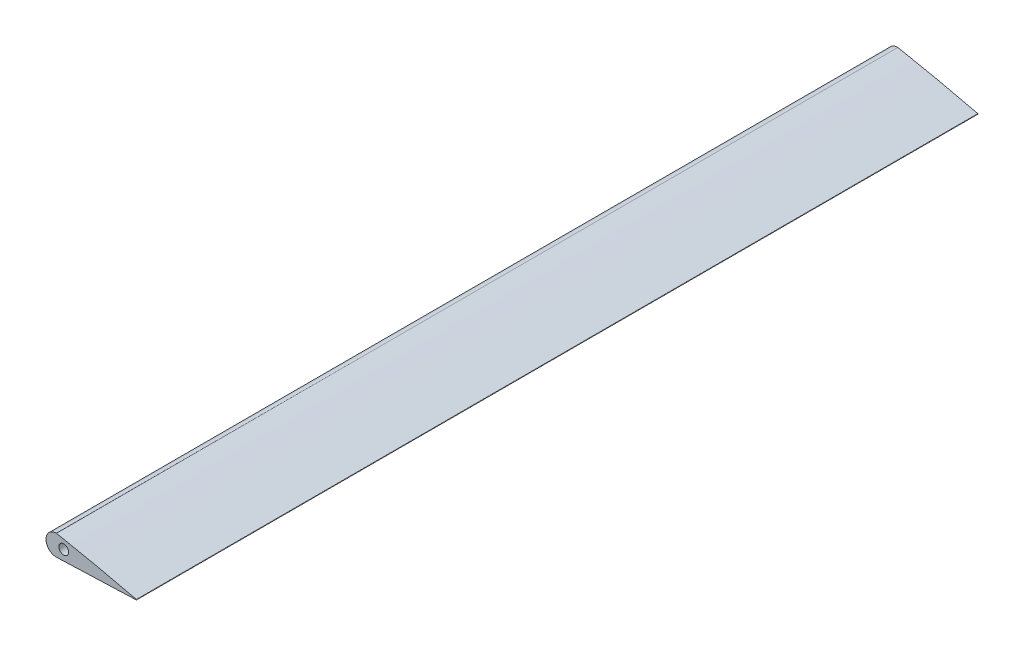
SolidWorks part; units mm, degrees
ref_plane "Front Plane" through (0, 0, 0) normal (0, 0, 1) x (1, 0, 0)
ref_plane "Top Plane" through (0, 0, 0) normal (0, 1, 0) x (1, 0, 0)
ref_plane "Right Plane" through (0, 0, 0) normal (1, 0, 0) x (0, 0, -1)
curve "Curve1"
  spline degree 3 poles (164, 0.0982, 0) (163.4533, 0.2279, 0) (162.3601, 0.4871, 0) (160.7202, 0.8748, 0) (159.0803, 1.2611, 0) (156.8943, 1.7719, 0) (154.162, 2.401, 0) (150.8818, 3.1375, 0) (147.6017, 3.8566, 0) (144.3217, 4.5599, 0) (141.0417, 5.2462, 0) (137.7618, 5.9156, 0) (134.4817, 6.5665, 0) (131.2018, 7.1999, 0) (127.9217, 7.8138, 0) (124.6417, 8.4092, 0) (121.3616, 8.9846, 0) (118.0816, 9.5413, 0) (114.8016, 10.0781, 0) (111.5216, 10.595, 0) (108.2417, 11.091, 0) (104.9617, 11.5629, 0) (101.6818, 12.0102, 0) (98.4017, 12.4297, 0) (95.1217, 12.8205, 0) (91.8415, 13.1818, 0) (88.5614, 13.5136, 0) (85.2813, 13.8159, 0) (82.0012, 14.0887, 0) (78.7211, 14.3317, 0) (75.441, 14.5432, 0) (72.1609, 14.7199, 0) (68.8807, 14.8594, 0) (65.6005, 14.9592, 0) (62.3202, 15.0161, 0) (59.04, 15.033, 0) (55.7598, 15.0128, 0) (52.4797, 14.9596, 0) (49.1996, 14.8756, 0) (45.9192, 14.7668, 0) (42.6385, 14.6188, 0) (39.3574, 14.416, 0) (36.0758, 14.1416, 0) (32.7935, 13.7797, 0) (29.5117, 13.3118, 0) (26.2304, 12.7369, 0) (22.9482, 12.0591, 0) (19.664, 11.2714, 0) (16.3781, 10.3517, 0) (13.0927, 9.2716, 0) (10.3582, 8.2399, 0) (8.1787, 7.2692, 0) (6.5271, 6.4236, 0) (4.8606, 5.419, 0) (3.3222, 4.2467, 0) (2.1668, 3.1342, 0) (1.2848, 2.24, 0) (0.7248, 1.5863, 0) (0.3565, 1.0237, 0) (0.1763, 0.6552, 0) (0.0613, 0.3376, 0) (-0.0429, -0.1211, 0) (0.0101, -0.5985, 0) (0.1762, -1.0141, 0) (0.3547, -1.3445, 0) (0.7171, -1.8262, 0) (1.2698, -2.3368, 0) (2.1318, -2.9202, 0) (3.3549, -3.3928, 0) (4.9153, -3.7072, 0) (6.5542, -4.033, 0) (8.1953, -4.2835, 0) (10.3823, -4.5154, 0) (13.1186, -4.6727, 0) (16.3989, -4.8285, 0) (19.6795, -4.9221, 0) (22.9598, -4.9665, 0) (26.2401, -4.9679, 0) (29.5202, -4.9328, 0) (32.8003, -4.8689, 0) (36.0803, -4.7827, 0) (39.3602, -4.679, 0) (42.6401, -4.563, 0) (45.9201, -4.4399, 0) (49.2, -4.3141, 0) (52.48, -4.1907, 0) (55.76, -4.07, 0) (59.04, -3.9501, 0) (62.32, -3.8313, 0) (65.6, -3.7121, 0) (68.88, -3.5923, 0) (72.16, -3.4722, 0) (75.44, -3.3513, 0) (78.72, -3.2307, 0) (82, -3.1097, 0) (85.28, -2.989, 0) (88.56, -2.8685, 0) (91.84, -2.7482, 0) (95.12, -2.6278, 0) (98.4, -2.5074, 0) (101.68, -2.387, 0) (104.96, -2.2667, 0) (108.24, -2.1461, 0) (111.52, -2.0255, 0) (114.8, -1.9053, 0) (118.08, -1.7846, 0) (121.36, -1.6644, 0) (124.64, -1.5437, 0) (127.92, -1.4234, 0) (131.2, -1.3027, 0) (134.48, -1.1825, 0) (137.76, -1.0618, 0) (141.04, -0.9416, 0) (144.32, -0.8209, 0) (147.6, -0.7007, 0) (150.88, -0.58, 0) (154.16, -0.4598, 0) (156.8933, -0.3592, 0) (159.08, -0.279, 0) (160.72, -0.2188, 0) (162.36, -0.1586, 0) (163.4533, -0.1184, 0) (164, -0.0982, 0) knots 0 0 0 0 0.005028 0.010055 0.015081 0.020105 0.030145 0.040174 0.050191 0.060198 0.070194 0.08018 0.090156 0.100121 0.110076 0.12002 0.129954 0.139879 0.149793 0.159699 0.169594 0.17948 0.189355 0.199219 0.209073 0.218917 0.228751 0.238577 0.248396 0.258207 0.268012 0.277811 0.287604 0.297393 0.307179 0.316964 0.326749 0.336535 0.346322 0.356113 0.365908 0.375711 0.385531 0.395376 0.405259 0.415192 0.425184 0.435248 0.445412 0.455711 0.466191 0.471552 0.477055 0.482787 0.488946 0.494316 0.497126 0.500187 0.502001 0.503128 0.50385 0.50502 0.507318 0.507987 0.509024 0.510668 0.513358 0.515716 0.519949 0.524973 0.529954 0.534903 0.539824 0.54963 0.559425 0.569214 0.579 0.588784 0.59857 0.608356 0.618144 0.627933 0.637724 0.647515 0.657307 0.667099 0.67689 0.686681 0.696472 0.706263 0.716054 0.725846 0.735637 0.745428 0.755219 0.765011 0.774802 0.784593 0.794384 0.804176 0.813967 0.823758 0.833549 0.84334 0.853132 0.862923 0.872714 0.882505 0.892297 0.902088 0.911879 0.92167 0.931461 0.941253 0.951044 0.960835 0.970626 0.980418 0.985313 0.990209 0.995104 1 1 1 1
sketch "Sketch2" plane through (0, 0, 0) normal (0, 0, 1) x (1, 0, 0)
  line L0 (0, 0) -> (164.0777, 0) construction
  arc A0 (164, 0.0982) -> (164, -0.0982) centre (163.9767, 0) cw
  spline S0 degree 3 poles (1530.9533, 3736.1944) (464.6242, -85.7653) (314.6036, -35.5074) (160.7202, 0.8748) (159.0803, 1.2611) (156.8943, 1.7719) (154.162, 2.401) (150.8818, 3.1375) (147.6017, 3.8566) (144.3217, 4.5599) (141.0417, 5.2462) (137.7618, 5.9156) (134.4817, 6.5665) (131.2018, 7.1999) (127.9217, 7.8138) (124.6417, 8.4092) (121.3616, 8.9846) (118.0816, 9.5413) (114.8016, 10.0781) (111.5216, 10.595) (108.2417, 11.091) (104.9617, 11.5629) (101.6818, 12.0102) (98.4017, 12.4297) (95.1217, 12.8205) (91.8415, 13.1818) (88.5614, 13.5136) (85.2813, 13.8159) (82.0012, 14.0887) (78.7211, 14.3317) (75.441, 14.5432) (72.1609, 14.7199) (68.8807, 14.8594) (65.6005, 14.9592) (62.3202, 15.0161) (59.04, 15.033) (55.7598, 15.0128) (52.4797, 14.9596) (49.1996, 14.8756) (45.9192, 14.7668) (42.6385, 14.6188) (39.3574, 14.416) (36.0758, 14.1416) (32.7935, 13.7797) (29.5117, 13.3118) (26.2304, 12.7369) (22.9482, 12.0591) (19.664, 11.2714) (16.3781, 10.3517) (13.0927, 9.2716) (10.3582, 8.2399) (8.1787, 7.2692) (6.5271, 6.4236) (4.8606, 5.419) (3.3222, 4.2467) (2.1668, 3.1342) (1.2848, 2.24) (0.7248, 1.5863) (0.3565, 1.0237) (0.1763, 0.6552) (0.0613, 0.3376) (-0.0429, -0.1211) (0.0101, -0.5985) (0.1762, -1.0141) (0.3547, -1.3445) (0.7171, -1.8262) (1.2698, -2.3368) (2.1318, -2.9202) (3.3549, -3.3928) (4.9153, -3.7072) (6.5542, -4.033) (8.1953, -4.2835) (10.3823, -4.5154) (13.1186, -4.6727) (16.3989, -4.8285) (19.6795, -4.9221) (22.9598, -4.9665) (26.2401, -4.9679) (29.5202, -4.9328) (32.8003, -4.8689) (36.0803, -4.7827) (39.3602, -4.679) (42.6401, -4.563) (45.9201, -4.4399) (49.2, -4.3141) (52.48, -4.1907) (55.76, -4.07) (59.04, -3.9501) (62.32, -3.8313) (65.6, -3.7121) (68.88, -3.5923) (72.16, -3.4722) (75.44, -3.3513) (78.72, -3.2307) (82, -3.1097) (85.28, -2.989) (88.56, -2.8685) (91.84, -2.7482) (95.12, -2.6278) (98.4, -2.5074) (101.68, -2.387) (104.96, -2.2667) (108.24, -2.1461) (111.52, -2.0255) (114.8, -1.9053) (118.08, -1.7846) (121.36, -1.6644) (124.64, -1.5437) (127.92, -1.4234) (131.2, -1.3027) (134.48, -1.1825) (137.76, -1.0618) (141.04, -0.9416) (144.32, -0.8209) (147.6, -0.7007) (150.88, -0.58) (154.16, -0.4598) (156.8933, -0.3592) (159.08, -0.279) (160.72, -0.2188) (405.1494, 8.7432) (648.7084, 26.4949) (1034.8655, -3850.8932) knots -1.400043 -1.400043 -1.400043 -1.400043 0.005028 0.010055 0.015081 0.020105 0.030145 0.040174 0.050191 0.060198 0.070194 0.08018 0.090156 0.100121 0.110076 0.12002 0.129954 0.139879 0.149793 0.159699 0.169594 0.17948 0.189355 0.199219 0.209073 0.218917 0.228751 0.238577 0.248396 0.258207 0.268012 0.277811 0.287604 0.297393 0.307179 0.316964 0.326749 0.336535 0.346322 0.356113 0.365908 0.375711 0.385531 0.395376 0.405259 0.415192 0.425184 0.435248 0.445412 0.455711 0.466191 0.471552 0.477055 0.482787 0.488946 0.494316 0.497126 0.500187 0.502001 0.503128 0.50385 0.50502 0.507318 0.507987 0.509024 0.510668 0.513358 0.515716 0.519949 0.524973 0.529954 0.534903 0.539824 0.54963 0.559425 0.569214 0.579 0.588784 0.59857 0.608356 0.618144 0.627933 0.637724 0.647515 0.657307 0.667099 0.67689 0.686681 0.696472 0.706263 0.716054 0.725846 0.735637 0.745428 0.755219 0.765011 0.774802 0.784593 0.794384 0.804176 0.813967 0.823758 0.833549 0.84334 0.853132 0.862923 0.872714 0.882505 0.892297 0.902088 0.911879 0.92167 0.931461 0.941253 0.951044 0.960835 0.970626 0.980418 0.985313 0.990209 0.995104 3.174268 3.174268 3.174268 3.174268 only from (164, 0.0982) to (164, -0.0982) construction
  spline S1 degree 3 poles (164, 0.0982) (163.4533, 0.2279) (162.3601, 0.4871) (160.7202, 0.8748) (159.0803, 1.2611) (156.8943, 1.7719) (154.162, 2.401) (150.8818, 3.1375) (147.6017, 3.8566) (144.3217, 4.5599) (141.0417, 5.2462) (137.7618, 5.9156) (134.4817, 6.5665) (131.2018, 7.1999) (127.9217, 7.8138) (124.6417, 8.4092) (121.3616, 8.9846) (118.0816, 9.5413) (114.8016, 10.0781) (111.5216, 10.595) (108.2417, 11.091) (104.9617, 11.5629) (101.6818, 12.0102) (98.4017, 12.4297) (95.1217, 12.8205) (91.8415, 13.1818) (88.5614, 13.5136) (85.2813, 13.8159) (82.0012, 14.0887) (78.7211, 14.3317) (75.441, 14.5432) (72.1609, 14.7199) (68.8807, 14.8594) (65.6005, 14.9592) (62.3202, 15.0161) (59.04, 15.033) (55.7598, 15.0128) (52.4797, 14.9596) (49.1996, 14.8756) (45.9192, 14.7668) (42.6385, 14.6188) (39.3574, 14.416) (36.0758, 14.1416) (32.7935, 13.7797) (29.5117, 13.3118) (26.2304, 12.7369) (22.9482, 12.0591) (19.664, 11.2714) (16.3781, 10.3517) (13.0927, 9.2716) (10.3582, 8.2399) (8.1787, 7.2692) (6.5271, 6.4236) (4.8606, 5.419) (3.3222, 4.2467) (2.1668, 3.1342) (1.2848, 2.24) (0.7248, 1.5863) (0.3565, 1.0237) (0.1763, 0.6552) (0.0613, 0.3376) (-0.0429, -0.1211) (0.0101, -0.5985) (0.1762, -1.0141) (0.3547, -1.3445) (0.7171, -1.8262) (1.2698, -2.3368) (2.1318, -2.9202) (3.3549, -3.3928) (4.9153, -3.7072) (6.5542, -4.033) (8.1953, -4.2835) (10.3823, -4.5154) (13.1186, -4.6727) (16.3989, -4.8285) (19.6795, -4.9221) (22.9598, -4.9665) (26.2401, -4.9679) (29.5202, -4.9328) (32.8003, -4.8689) (36.0803, -4.7827) (39.3602, -4.679) (42.6401, -4.563) (45.9201, -4.4399) (49.2, -4.3141) (52.48, -4.1907) (55.76, -4.07) (59.04, -3.9501) (62.32, -3.8313) (65.6, -3.7121) (68.88, -3.5923) (72.16, -3.4722) (75.44, -3.3513) (78.72, -3.2307) (82, -3.1097) (85.28, -2.989) (88.56, -2.8685) (91.84, -2.7482) (95.12, -2.6278) (98.4, -2.5074) (101.68, -2.387) (104.96, -2.2667) (108.24, -2.1461) (111.52, -2.0255) (114.8, -1.9053) (118.08, -1.7846) (121.36, -1.6644) (124.64, -1.5437) (127.92, -1.4234) (131.2, -1.3027) (134.48, -1.1825) (137.76, -1.0618) (141.04, -0.9416) (144.32, -0.8209) (147.6, -0.7007) (150.88, -0.58) (154.16, -0.4598) (156.8933, -0.3592) (159.08, -0.279) (160.72, -0.2188) (162.36, -0.1586) (163.4533, -0.1184) (164, -0.0982) knots 0 0 0 0 0.005028 0.010055 0.015081 0.020105 0.030145 0.040174 0.050191 0.060198 0.070194 0.08018 0.090156 0.100121 0.110076 0.12002 0.129954 0.139879 0.149793 0.159699 0.169594 0.17948 0.189355 0.199219 0.209073 0.218917 0.228751 0.238577 0.248396 0.258207 0.268012 0.277811 0.287604 0.297393 0.307179 0.316964 0.326749 0.336535 0.346322 0.356113 0.365908 0.375711 0.385531 0.395376 0.405259 0.415192 0.425184 0.435248 0.445412 0.455711 0.466191 0.471552 0.477055 0.482787 0.488946 0.494316 0.497126 0.500187 0.502001 0.503128 0.50385 0.50502 0.507318 0.507987 0.509024 0.510668 0.513358 0.515716 0.519949 0.524973 0.529954 0.534903 0.539824 0.54963 0.559425 0.569214 0.579 0.588784 0.59857 0.608356 0.618144 0.627933 0.637724 0.647515 0.657307 0.667099 0.67689 0.686681 0.696472 0.706263 0.716054 0.725846 0.735637 0.745428 0.755219 0.765011 0.774802 0.784593 0.794384 0.804176 0.813967 0.823758 0.833549 0.84334 0.853132 0.862923 0.872714 0.882505 0.892297 0.902088 0.911879 0.92167 0.931461 0.941253 0.951044 0.960835 0.970626 0.980418 0.985313 0.990209 0.995104 1 1 1 1
extrude "Boss-Extrude1" add sketch "Sketch2" along normal blind 1246.6
sketch "Sketch3" plane through (0, 0, 1246.6) normal (0, 0, 1) x (1, 0, 0)
  line L0 (0, 0) -> (164.0777, 0) construction
  line L2 (-0.0541, 26.1225) -> (131.2777, 26.1225)
  line L3 (-0.0541, 26.1225) -> (-0.0541, -6.5054)
  line L4 (-0.0541, -6.5054) -> (131.2777, -6.5054)
  line L5 (131.2777, 26.1225) -> (131.2777, -6.5054)
  arc A0 (164, -0.0982) -> (164, 0.0982) centre (163.9767, 0) ccw construction
  dimension "D1" = 32.8
extrude "Cut-Extrude1" cut sketch "Sketch3" against normal blind 1246.6
sketch "Sketch4" plane through (0, 0, 0) normal (0, 1, 0) x (1, 0, 0)
  line L0 (131.2777, -1246.6) -> (164, -1246.6) construction
  line L1 (164, 0) -> (62.7392, 0)
  line L2 (164, 0) -> (164, -902.35)
  line L3 (164, -902.35) -> (62.7392, -902.35)
  line L4 (62.7392, 0) -> (62.7392, -902.35)
  dimension "D1" = 344.25
extrude "Cut-Extrude2" cut sketch "Sketch4" along normal blind 1246.6 and the other way blind 1246.6 flip side to cut
sketch "Sketch6" plane through (0, 0, 0) normal (0, 1, 0) x (1, 0, 0)
  line L0 (164, 0) -> (-0.0103, 0) construction
  line L1 (178.1912, -1000.846) -> (-14.2341, -1000.846)
  line L2 (178.1912, -1000.846) -> (178.1912, -344.25)
  line L3 (178.1912, -344.25) -> (-14.2341, -344.25)
  line L4 (-14.2341, -1000.846) -> (-14.2341, -344.25)
  dimension "D1" = 344.25
extrude "Cut-Extrude4" cut sketch "Sketch6" against normal blind 244.6 and the other way blind 244.6
sketch "Sketch7" plane through (0, 0, 0) normal (0, 0, -1) x (-1, 0, 0)
  line L0 (-131.2777, 7.1822) -> (-131.2777, -1.3) construction
  line L3 (-164, 0.0982) -> (-164, -0.0982)
  line L4 (-131.2777, -1.3) -> (-131.2777, 7.1822)
  line L5 (-164, 0.0982) -> (-164, -0.0982)
  arc A0 (-131.2777, 7.1822) -> (-131.2777, -1.3) centre (-131.2777, 2.9411) cw
  spline S2 degree 3 poles (1154.3146, -3728.2178) (371.2964, -35.0767) (103.9266, 53.881) (-137.7618, 5.9156) (-141.0417, 5.2462) (-144.3217, 4.5599) (-147.6017, 3.8566) (-150.8818, 3.1375) (-154.162, 2.401) (-156.8943, 1.7719) (-159.0803, 1.2611) (-160.7202, 0.8748) (-314.6033, -35.5073) (-464.6237, -85.7651) (-1530.9472, 3736.1725) knots -2.175437 -2.175437 -2.175437 -2.175437 0.009729 0.019705 0.029691 0.039688 0.049694 0.059712 0.06974 0.07978 0.084804 0.08983 0.094857 1.499925 1.499925 1.499925 1.499925 only from (-131.2777, 7.1822) to (-164, 0.0982)
  spline S3 degree 3 poles (-1034.8785, -3851.0237) (-648.7138, 26.4953) (-405.1521, 8.7433) (-160.72, -0.2188) (-159.08, -0.279) (-156.8933, -0.3592) (-154.16, -0.4598) (-150.88, -0.58) (-147.6, -0.7007) (-144.32, -0.8209) (-141.04, -0.9416) (-137.76, -1.0618) (176.8115, -12.6381) (490.537, -17.4422) (663.1282, -3835.4366) knots -1.271973 -1.271973 -1.271973 -1.271973 0.907215 0.912111 0.917006 0.921902 0.931693 0.941485 0.951276 0.961067 0.970858 0.980649 0.990441 3.787976 3.787976 3.787976 3.787976 only from (-164, -0.0982) to (-131.2777, -1.3)
  spline S4 degree 3 poles (-131.2777, 7.1822) (-132.3457, 6.979) (-134.5075, 6.5614) (-137.7618, 5.9156) (-141.0417, 5.2462) (-144.3217, 4.5599) (-147.6017, 3.8566) (-150.8818, 3.1375) (-154.162, 2.401) (-156.8943, 1.7719) (-159.0803, 1.2611) (-160.7202, 0.8748) (-162.3601, 0.4871) (-163.4533, 0.2279) (-164, 0.0982) knots 0 0 0 0 0.009729 0.019705 0.029691 0.039688 0.049694 0.059712 0.06974 0.07978 0.084804 0.08983 0.094857 0.099885 0.099885 0.099885 0.099885
  spline S5 degree 3 poles (-164, -0.0982) (-163.4533, -0.1184) (-162.36, -0.1586) (-160.72, -0.2188) (-159.08, -0.279) (-156.8933, -0.3592) (-154.16, -0.4598) (-150.88, -0.58) (-147.6, -0.7007) (-144.32, -0.8209) (-141.04, -0.9416) (-137.76, -1.0618) (-134.5059, -1.1816) (-132.3451, -1.2608) (-131.2777, -1.3) knots 0.90232 0.90232 0.90232 0.90232 0.907215 0.912111 0.917006 0.921902 0.931693 0.941485 0.951276 0.961067 0.970858 0.980649 0.990441 1 1 1 1
  dimension "D1" = 0
extrude "Boss-Extrude2" add sketch "Sketch7" against normal blind 344.25
sketch "Sketch8" plane through (0, 0, 0) normal (0, 0, -1) x (-1, 0, 0)
  line L0 (-131.2777, 7.1822) -> (-131.2777, -1.3) construction
  line L1 (-131.2777, 2.9411) -> (-145.2776, 2.9411) construction
  circle A0 centre (-134.2777, 2.9411) radius 2
  dimension "D1" = 4
  dimension "D2" = 3
extrude "Cut-Extrude5" cut sketch "Sketch8" against normal blind 440.25
sketch "Sketch9" plane through (0, 0, 0) normal (0, 0, -1) x (-1, 0, 0)
  line L1 (-164, 0.0982) -> (-164, -0.0982)
  line L2 (-164, 0.0982) -> (-164, -0.0982) construction
  line L3 (-164, 0.0982) -> (-164, -0.0982)
  arc A0 (-164, 0.0982) -> (-164, -0.0982) centre (-163.9767, 0) ccw
  arc A2 (-131.2777, -1.3) -> (-131.2777, 7.1822) centre (-131.2777, 2.9411) ccw
  spline S4 degree 3 poles (435.3817, -816.7688) (164.1268, 13.8874) (8.8334, 35.0088) (-137.7618, 5.9156) (-141.0417, 5.2462) (-144.3217, 4.5599) (-147.6017, 3.8566) (-150.8818, 3.1375) (-154.162, 2.401) (-156.8943, 1.7719) (-159.0803, 1.2611) (-160.7202, 0.8748) (-257.2425, -21.9457) (-351.9191, -50.1236) (-668.9577, 863.2222) knots -1.307821 -1.307821 -1.307821 -1.307821 0.009729 0.019705 0.029691 0.039688 0.049694 0.059712 0.06974 0.07978 0.084804 0.08983 0.094857 0.972431 0.972431 0.972431 0.972431 only from (-131.2777, 7.1822) to (-164, 0.0982)
  spline S5 degree 3 poles (-643.4759, -877.653) (-461.0803, 14.1296) (-311.2347, 5.2998) (-160.72, -0.2188) (-159.08, -0.279) (-156.8933, -0.3592) (-154.16, -0.4598) (-150.88, -0.58) (-147.6, -0.7007) (-144.32, -0.8209) (-141.04, -0.9416) (-137.76, -1.0618) (52.5424, -8.0649) (241.8416, -12.5754) (399.5009, -848.8098) knots -0.430908 -0.430908 -0.430908 -0.430908 0.907215 0.912111 0.917006 0.921902 0.931693 0.941485 0.951276 0.961067 0.970858 0.980649 0.990441 2.675095 2.675095 2.675095 2.675095 only from (-164, -0.0982) to (-131.2777, -1.3)
  dimension "D1" = 0
extrude "Boss-Extrude3" add sketch "Sketch9" against normal up to vertex (344.25 mm away) up to point (164, 0.0982, 344.25)
